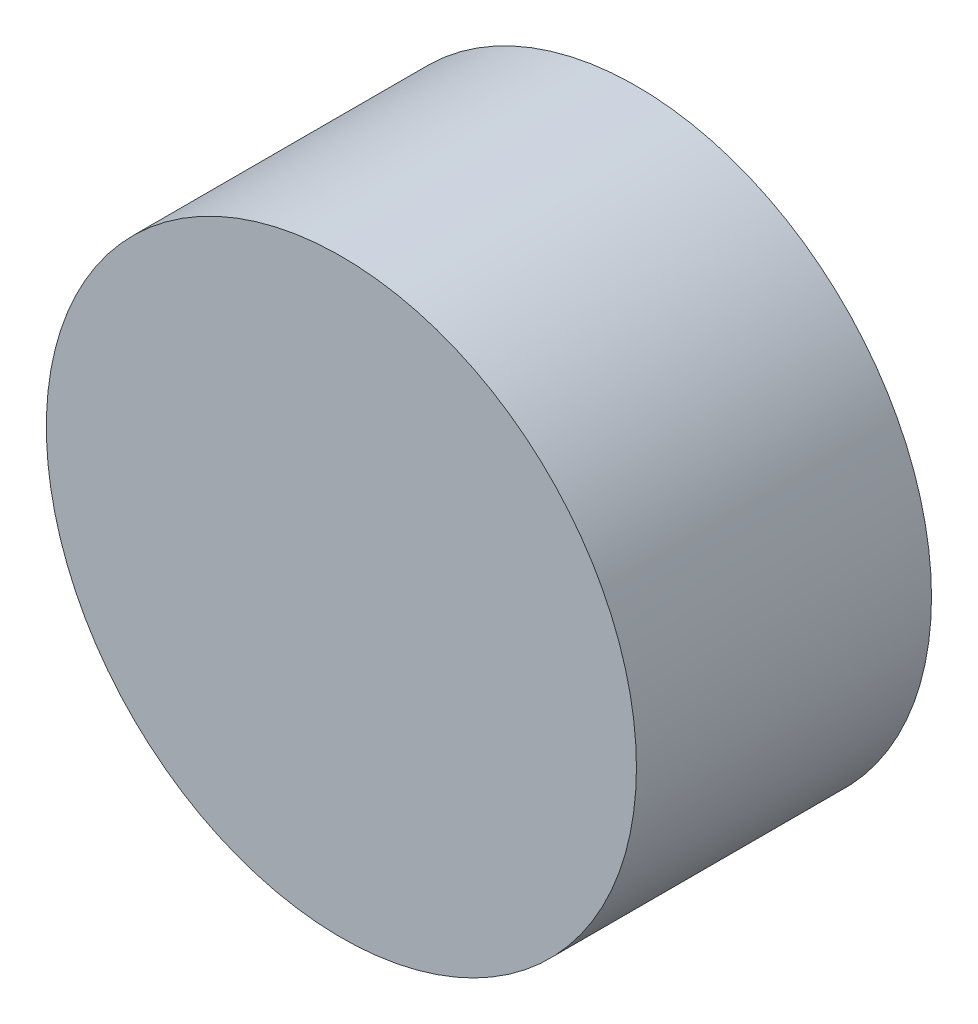
SolidWorks part; units mm, degrees
ref_plane "Front Plane" through (0, 0, 0) normal (0, 0, 1) x (1, 0, 0)
ref_plane "Top Plane" through (0, 0, 0) normal (0, 1, 0) x (1, 0, 0)
ref_plane "Right Plane" through (0, 0, 0) normal (1, 0, 0) x (0, 0, -1)
sketch "Sketch1" plane through (0, 0, 0) normal (0, 0, 1) x (1, 0, 0)
  circle A0 centre (0, 0) radius 15
  dimension "D1" = 30
extrude "Boss-Extrude1" add sketch "Sketch1" along normal blind 15 contours A0
ref_axis "Axis1" through (0, 0, 15) along (0, 0, -1)
